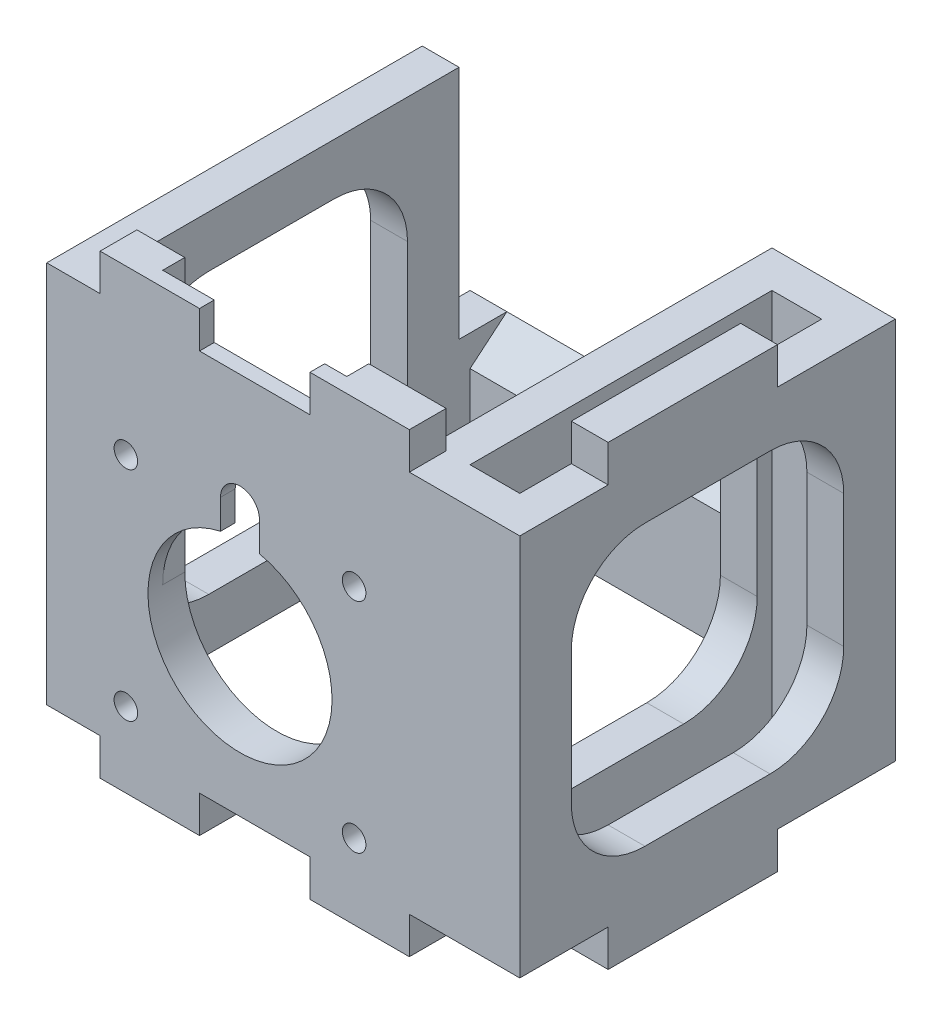
SolidWorks part; units mm, degrees
ref_plane "Plan de face" through (0, 0, 0) normal (0, 0, 1) x (1, 0, 0)
ref_plane "Plan de dessus" through (0, 0, 0) normal (0, 1, 0) x (1, 0, 0)
ref_plane "Plan de droite" through (0, 0, 0) normal (1, 0, 0) x (0, 0, -1)
sketch "Esquisse1" plane through (0, 0, 0) normal (0, 1, 0) x (1, 0, 0)
  line L1 (21.25, 23.75) -> (-21.25, 23.75)
  line L2 (21.25, 23.75) -> (21.25, -23.75)
  line L3 (21.25, -23.75) -> (-21.25, -23.75)
  line L4 (-21.25, 23.75) -> (-21.25, -23.75)
  line L5 (21.25, 23.75) -> (-21.25, -23.75) construction
  line L6 (21.25, -23.75) -> (-21.25, 23.75) construction
  point P0 (0, 0)
  dimension "D1" = 47.5
  dimension "D2" = 42.5
extrude "Extru.-Mince1" add sketch "Esquisse1" along normal blind 20 thin thin type one direction wall 5
sketch "Esquisse3" plane through (0, 0, 0) normal (0, -1, 0) x (1, 0, 0)
  line L0 (26.25, 28.75) -> (38, 28.75)
  line L1 (38, 28.75) -> (38, -22.25)
  line L3 (38, -22.25) -> (21.25, -22.25)
  line L4 (21.25, 23.75) -> (21.25, -23.75) construction
  line L5 (26.25, 28.75) -> (0, 28.75)
  line L6 (0, 28.75) -> (-26.25, 28.75)
  line L7 (-26.25, 28.75) -> (-62, 28.75)
  line L8 (-62, 28.75) -> (-62, -22.25)
  line L9 (-62, -22.25) -> (-21.25, -22.25)
  line L10 (-26.25, -28.75) -> (-26.25, 28.75) construction
  line L11 (33, 23.75) -> (33, -17.25)
  line L12 (33, -17.25) -> (26.25, -17.25)
  line L13 (26.25, 28.75) -> (26.25, -28.75) construction
  line L14 (26.25, -17.25) -> (26.25, 23.75)
  line L15 (26.25, 23.75) -> (33, 23.75)
  line L16 (-57, -17.25) -> (-26.25, -17.25)
  line L17 (-21.25, -23.75) -> (-21.25, 23.75) construction
  line L18 (-57, -17.25) -> (-57, 23.75)
  line L19 (-57, 23.75) -> (-26.25, 23.75)
  line L20 (-21.25, 23.75) -> (21.25, 23.75)
  line L21 (21.25, 23.75) -> (21.25, -22.25)
  line L22 (-21.25, 23.75) -> (-21.25, -22.25)
  line L23 (-26.25, 23.75) -> (-26.25, -17.25)
  line L24 (-26.25, 28.75) -> (26.25, 28.75) construction
  point P6 (26.25, 28.75)
  point P7 (-26.25, 28.75)
  dimension "D1" = 51
  dimension "D2" = 38
  dimension "D3" = 62
  dimension "D4" = 5
  dimension "D5" = 5
  dimension "D6" = 5
  dimension "D7" = 5
  dimension "D8" = 5
  dimension "D9" = 5
extrude "Boss.-Extru.1" add sketch "Esquisse3" against normal blind 52
sketch "Esquisse6" plane through (0, 52, 0) normal (0, 1, 0) x (1, 0, 0)
  line L0 (38, 6.25) -> (33, 6.25)
  line L1 (38, 22.25) -> (38, -28.75) construction
  line L2 (33, 17.25) -> (33, -23.75) construction
  line L3 (33, 6.25) -> (33, -16.75)
  line L4 (33, -16.75) -> (38, -16.75)
  line L5 (38, -16.75) -> (38, 6.25)
  line L6 (23, -28.75) -> (23, -23.75)
  line L7 (38, -28.75) -> (-62, -28.75) construction
  line L8 (33, -23.75) -> (26.25, -23.75) construction
  line L9 (23, -23.75) -> (9.5, -23.75)
  line L10 (-21.25, -23.75) -> (21.25, -23.75) construction
  line L11 (9.5, -23.75) -> (9.5, -28.75)
  line L12 (9.5, -28.75) -> (23, -28.75)
  line L13 (-5.5, -28.75) -> (-5.5, -23.75)
  line L14 (-5.5, -23.75) -> (-19, -23.75)
  line L15 (-19, -23.75) -> (-19, -28.75)
  line L16 (-19, -28.75) -> (-5.5, -28.75)
  line L17 (-34, -28.75) -> (-34, -23.75)
  line L18 (-34, -23.75) -> (-47.5, -23.75)
  line L19 (-47.5, -23.75) -> (-47.5, -28.75)
  line L20 (-47.5, -28.75) -> (-34, -28.75)
  line L23 (-47.5, 22.25) -> (-34, 22.25)
  line L24 (-47.5, 17.25) -> (-47.5, 22.25)
  line L25 (-34, 17.25) -> (-47.5, 17.25)
  line L26 (-34, 22.25) -> (-34, 17.25)
  line L28 (-62, -16.75) -> (-62, 6.25)
  line L29 (-57, -16.75) -> (-62, -16.75)
  line L30 (-57, 6.25) -> (-57, -16.75)
  line L31 (-62, 6.25) -> (-57, 6.25)
  point P6 (38, -5.25)
  point P15 (38, -5.25)
  dimension "D1" = 23
  dimension "D2" = 13.5
  dimension "D3" = 15
  dimension "D5" = 23.5
  dimension "D6" = 12
  dimension "D4" = 3
extrude "Boss.-Extru.3" add sketch "Esquisse6" along normal blind 5
sketch "Esquisse2" plane through (0, 0, 28.75) normal (0, 0, 1) x (1, 0, 0)
  line L0 (-62, 0) -> (38, 0) construction
  line L1 (0, -0.0585) -> (0, 20) construction
  line L2 (-15.5, 5.2) -> (15.5, 5.2) construction
  line L3 (38, 52) -> (38, 0) construction
  line L4 (0, 36.2159) -> (0, 28.8659) construction
  line L5 (2.65, 36.2159) -> (2.65, 32.2159)
  line L6 (-62, 0) -> (38, 0) construction
  line L7 (0, 20) -> (33.7261, 20) construction
  line L8 (-15.5, 34.8) -> (15.5, 34.8) construction
  line L9 (-2.65, 36.2159) -> (-2.65, 32.2159)
  arc A0 (-2.65, 32.2159) -> (2.65, 32.2159) centre (0, 20) ccw
  circle A1 centre (-15.5, 5.2) radius 1.6
  circle A2 centre (15.5, 5.2) radius 1.6
  circle A3 centre (15.5, 34.8) radius 1.6
  circle A4 centre (-15.5, 34.8) radius 1.6
  arc A5 (2.65, 36.2159) -> (-2.65, 36.2159) centre (0, 36.2159) ccw
  point P6 (0, -0.0585)
  point P10 (0, 5.2)
  point P20 (0, 34.8)
  point P21 (0, 40.0585)
  point P24 (0, 32.5)
  dimension "D2" = 25
  dimension "D3" = 3.2
  dimension "D4" = 3.2
  dimension "D8" = 2.65
  dimension "D1" = 20
  dimension "D5" = 5.2
  dimension "D6" = 31
  dimension "D7" = 38
  dimension "D9" = 7.35
  dimension "D10" = 5.3
  dimension "D11" = 4
extrude "Enlèv. mat.-Extru.1" cut sketch "Esquisse2" against normal up to next
sketch "Esquisse4" plane through (0, 0, 23.75) normal (0, 0, -1) x (-1, 0, 0)
  line L0 (-12.5, 20) -> (-12.5, 57)
  line L2 (-23, 57) -> (-9.5, 57) construction
  line L3 (12.5, 57) -> (12.5, 20)
  line L4 (-12.5, 57) -> (12.5, 57)
  circle A0 centre (0, 20) radius 12.5 construction
  arc A1 (-12.5, 20) -> (12.5, 20) centre (0, 20) cw
  dimension "D1" = 25
extrude "Enlèv. mat.-Extru.2" cut sketch "Esquisse4" against normal blind 3
ref_plane "Plan1" through (0, 26, 0) normal (0, -1, 0) x (-1, 0, 0)
mirror "Symétrie1" about plane through (0, 26, 0) normal (0, -1, 0) of "Boss.-Extru.3"
ref_plane "Plan2" through (0, 0, 0) normal (1, 0, 0) x (0, 0, -1)
sketch "Esquisse7" plane through (38, 0, 0) normal (1, 0, 0) x (0, 0, -1)
  line L0 (-16.75, 0) -> (-28.75, 0) construction
  line L1 (-11.75, 45) -> (5.25, 45)
  line L2 (-21.75, 35) -> (-21.75, 17)
  line L3 (-11.75, 7) -> (5.25, 7)
  line L4 (15.25, 35) -> (15.25, 17)
  line L5 (-21.75, 45) -> (15.25, 7) construction
  line L6 (-21.75, 7) -> (15.25, 45) construction
  line L7 (-16.75, 52) -> (-28.75, 52) construction
  line L8 (22.25, 52) -> (22.25, 0) construction
  line L9 (-28.75, 52) -> (-28.75, 0) construction
  arc A0 (5.25, 7) -> (15.25, 17) centre (5.25, 17) ccw
  arc A1 (-21.75, 17) -> (-11.75, 7) centre (-11.75, 17) ccw
  arc A2 (5.25, 45) -> (15.25, 35) centre (5.25, 35) cw
  arc A3 (-11.75, 45) -> (-21.75, 35) centre (-11.75, 35) ccw
  point P0 (-3.25, 26)
  dimension "D5" = 10
  dimension "D1" = 7
  dimension "D2" = 7
  dimension "D3" = 7
  dimension "D4" = 7
extrude "Enlèv. mat.-Extru.3" cut sketch "Esquisse7" against normal through all
sketch "Esquisse8" plane through (0, 0, -22.25) normal (0, 0, -1) x (-1, 0, 0)
  line L0 (41.625, 33.5) -> (41.625, 18.5) construction
  line L1 (48.625, 33.5) -> (48.625, 18.5)
  line L2 (34.625, 33.5) -> (34.625, 18.5)
  line L3 (62, 52) -> (62, 0) construction
  line L5 (62, 26) -> (21.25, 26) construction
  line L6 (21.25, 52) -> (21.25, 20) construction
  arc A0 (48.625, 33.5) -> (34.625, 33.5) centre (41.625, 33.5) ccw
  arc A1 (34.625, 18.5) -> (48.625, 18.5) centre (41.625, 18.5) ccw
  point P2 (41.625, 26)
  dimension "D2" = 7
  dimension "D1" = 15
extrude "Enlèv. mat.-Extru.4" cut sketch "Esquisse8" against normal through all
sketch "Esquisse10" plane through (0, 52, 0) normal (0, 1, 0) x (1, 0, 0)
  line L0 (-26.25, -28.75) -> (-26.25, 22.25)
  line L1 (-19, -28.75) -> (-34, -28.75) construction
  line L2 (-34, 22.25) -> (-21.25, 22.25) construction
  line L3 (-26.25, 22.25) -> (-62, 22.25)
  line L4 (-62, 22.25) -> (-62, -28.75)
  line L5 (-62, -28.75) -> (-26.25, -28.75)
  line L6 (-26.25, 17.25) -> (-26.25, -23.75) construction
  point P6 (-26.25, -3.25)
  point P17 (-26.25, -3.25)
extrude "Enlèv. mat.-Extru.5" cut sketch "Esquisse10" against normal through all both and the other way through all
chamfer "Chanfrein1" distance 5 angle 40 1 edges at (0, 20, -23.75) first distance on face at (0, 20, -24.25)
